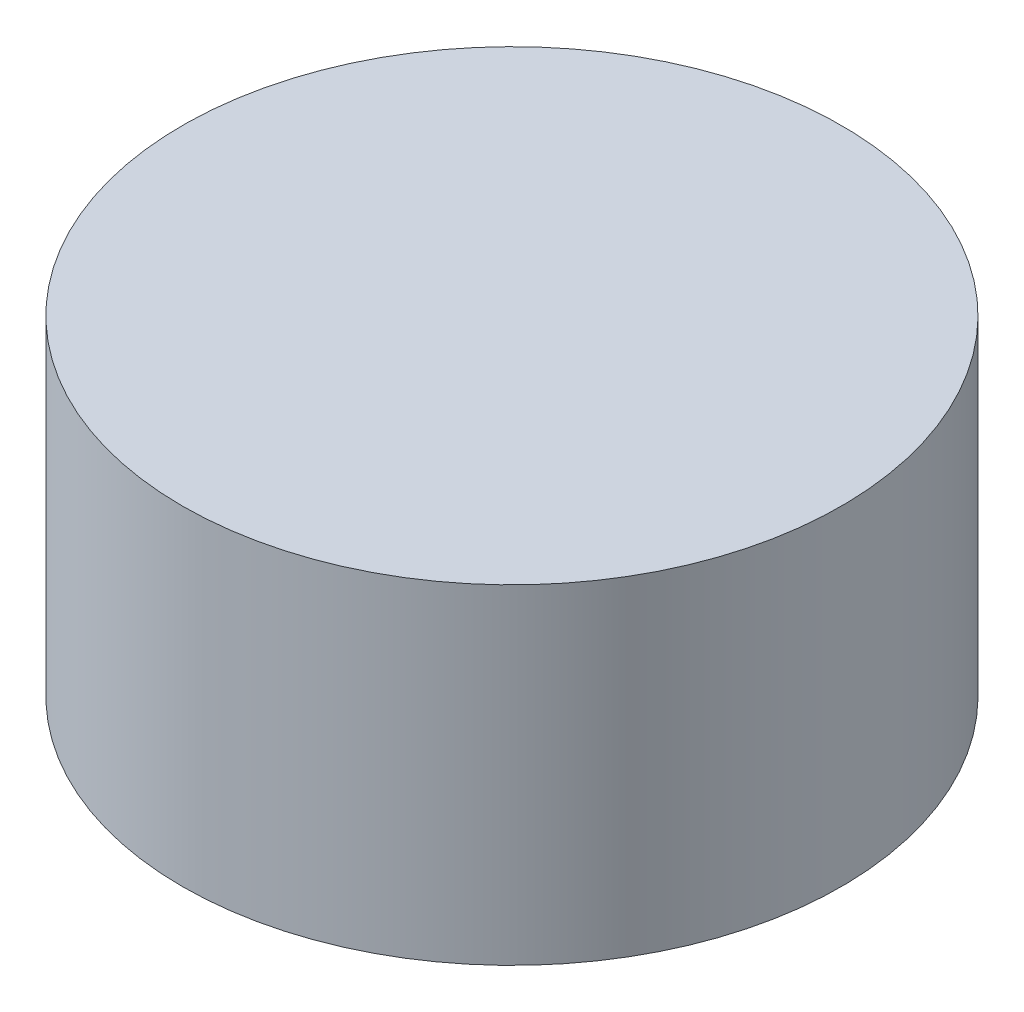
SolidWorks part; units mm, degrees
ref_plane "Front Plane" through (0, 0, 0) normal (0, 0, 1) x (1, 0, 0)
ref_plane "Top Plane" through (0, 0, 0) normal (0, 1, 0) x (1, 0, 0)
ref_plane "Right Plane" through (0, 0, 0) normal (1, 0, 0) x (0, 0, -1)
sketch "Sketch1" plane through (0, 0, 0) normal (0, 1, 0) x (1, 0, 0)
  circle A0 centre (0, 0) radius 70
  dimension "D1" = 140
extrude "Boss-Extrude1" add sketch "Sketch1" against normal blind 70
